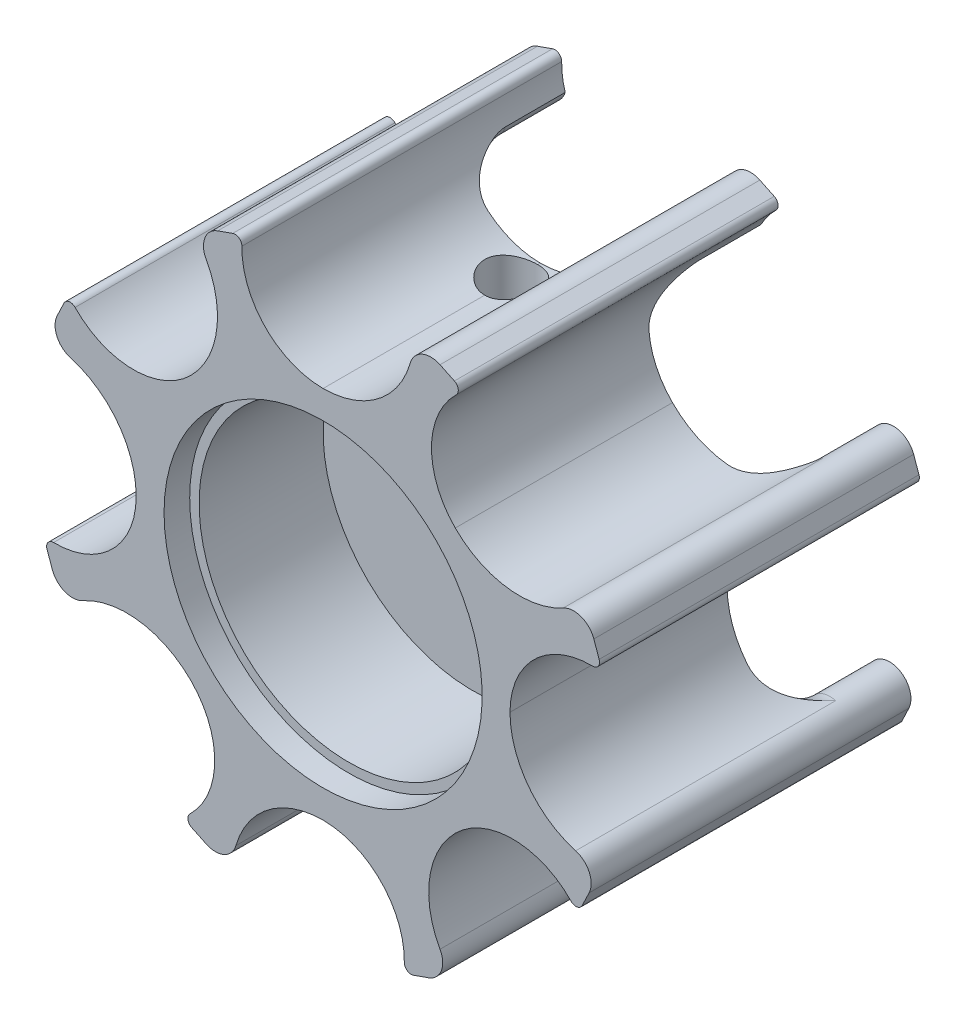
SolidWorks part; units mm, degrees
material "ABS"
ref_plane "前视基准面" through (0, 0, 0) normal (0, 0, 1) x (1, 0, 0)
ref_plane "上视基准面" through (0, 0, 0) normal (0, 1, 0) x (1, 0, 0)
ref_plane "右视基准面" through (0, 0, 0) normal (1, 0, 0) x (0, 0, -1)
sketch "草图1" plane through (0, 0, 0) normal (0, 0, 1) x (1, 0, 0)
  line L0 (0, 31.3575) -> (0, 0) construction
  line L1 (0, 0) -> (22.1731, 22.1731) construction
  line L4 (0, 31.3575) -> (22.1731, 22.1731) construction
  line L6 (11.6409, 26.5357) -> (12.5976, 28.8454) construction
  line L7 (21.7656, 23.184) -> (15.5687, 29.0018) construction
  line L8 (21.7656, 23.184) -> (27.9942, 29.8184) construction
  line L9 (15.357, 30.2989) -> (13.674, 31.1018)
  line L10 (32.2836, 10.5656) -> (31.6613, 12.3233)
  line L11 (30.2989, -15.357) -> (31.1018, -13.674)
  line L12 (10.5656, -32.2836) -> (12.3233, -31.6613)
  line L13 (-15.357, -30.2989) -> (-13.674, -31.1018)
  line L14 (-32.2836, -10.5656) -> (-31.6613, -12.3233)
  line L15 (-30.2989, 15.357) -> (-31.1018, 13.674)
  line L16 (-10.5656, 32.2836) -> (-12.3233, 31.6613)
  circle A0 centre (0, 0) radius 31.3575 construction
  arc A9 (15.5687, 29.0018) -> (15.4556, 15.4556) centre (22.1731, 22.1731) ccw
  circle A13 centre (0, 0) radius 40.9 construction
  arc A16 (15.5687, 29.0018) -> (15.357, 30.2989) centre (15.0125, 29.5769) ccw
  arc A17 (13.674, 31.1018) -> (10.1948, 29.5357) centre (12.5976, 28.8454) ccw
  arc A18 (0, 21.8575) -> (10.1948, 29.5357) centre (0, 32.4647) ccw
  arc A19 (31.5161, 9.4987) -> (21.8575, 0) centre (31.3575, 0) ccw
  arc A20 (31.5161, 9.4987) -> (32.2836, 10.5656) centre (31.5295, 10.2986) ccw
  arc A21 (31.6613, 12.3233) -> (28.0937, 13.6761) centre (29.3046, 11.4889) ccw
  arc A22 (15.4556, 15.4556) -> (28.0937, 13.6761) centre (22.956, 22.956) ccw
  arc A24 (29.0018, -15.5687) -> (15.4556, -15.4556) centre (22.1731, -22.1731) ccw
  arc A25 (29.0018, -15.5687) -> (30.2989, -15.357) centre (29.5769, -15.0125) ccw
  arc A26 (31.1018, -13.674) -> (29.5357, -10.1948) centre (28.8454, -12.5976) ccw
  arc A27 (21.8575, 0) -> (29.5357, -10.1948) centre (32.4647, 0) ccw
  arc A29 (9.4987, -31.5161) -> (0, -21.8575) centre (0, -31.3575) ccw
  arc A30 (9.4987, -31.5161) -> (10.5656, -32.2836) centre (10.2986, -31.5295) ccw
  arc A31 (12.3233, -31.6613) -> (13.6761, -28.0937) centre (11.4889, -29.3046) ccw
  arc A32 (15.4556, -15.4556) -> (13.6761, -28.0937) centre (22.956, -22.956) ccw
  arc A34 (-15.5687, -29.0018) -> (-15.4556, -15.4556) centre (-22.1731, -22.1731) ccw
  arc A35 (-15.5687, -29.0018) -> (-15.357, -30.2989) centre (-15.0125, -29.5769) ccw
  arc A36 (-13.674, -31.1018) -> (-10.1948, -29.5357) centre (-12.5976, -28.8454) ccw
  arc A37 (0, -21.8575) -> (-10.1948, -29.5357) centre (0, -32.4647) ccw
  arc A39 (-31.5161, -9.4987) -> (-21.8575, 0) centre (-31.3575, 0) ccw
  arc A40 (-31.5161, -9.4987) -> (-32.2836, -10.5656) centre (-31.5295, -10.2986) ccw
  arc A41 (-31.6613, -12.3233) -> (-28.0937, -13.6761) centre (-29.3046, -11.4889) ccw
  arc A42 (-15.4556, -15.4556) -> (-28.0937, -13.6761) centre (-22.956, -22.956) ccw
  arc A44 (-29.0018, 15.5687) -> (-15.4556, 15.4556) centre (-22.1731, 22.1731) ccw
  arc A45 (-29.0018, 15.5687) -> (-30.2989, 15.357) centre (-29.5769, 15.0125) ccw
  arc A46 (-31.1018, 13.674) -> (-29.5357, 10.1948) centre (-28.8454, 12.5976) ccw
  arc A47 (-21.8575, 0) -> (-29.5357, 10.1948) centre (-32.4647, 0) ccw
  arc A49 (-9.4987, 31.5161) -> (0, 21.8575) centre (0, 31.3575) ccw
  arc A50 (-9.4987, 31.5161) -> (-10.5656, 32.2836) centre (-10.2986, 31.5295) ccw
  arc A51 (-12.3233, 31.6613) -> (-13.6761, 28.0937) centre (-11.4889, 29.3046) ccw
  arc A52 (-15.4556, 15.4556) -> (-13.6761, 28.0937) centre (-22.956, 22.956) ccw
  point P98 (0, 0)
  dimension "D1" = 9.5
  dimension "D3" = 45
  dimension "D5" = 9.1
  dimension "D8" = 81.8
  dimension "D9" = 9.5
  dimension "D10" = 2.5
  dimension "D11" = 0.8
  dimension "D2" = 24
  dimension "D6" = 11.4
  dimension "D7" = 2.5
  dimension "D13" = 8.5
  dimension "D12" = 8
extrude "凸台-拉伸1" add sketch "草图1" along normal blind 27.5
sketch "草图2" plane through (0, 0, 0) normal (0, 0, -1) x (-1, 0, 0)
  line L0 (0, 0) -> (21.8575, 0) construction
  line L1 (0, 0) -> (15.4556, -15.4556) construction
  arc A0 (20.6575, 0) -> (24.8509, -8.4944) centre (31.3575, 0) ccw construction
  arc A1 (23.828, -11.1811) -> (14.6071, -14.6071) centre (22.956, -22.956) ccw construction
  arc A2 (23.828, -11.1811) -> (24.8509, -8.4944) centre (23.9388, -9.6852) ccw construction
  circle A3 centre (0, 0) radius 18.6
  arc A4 (28.0937, -13.6761) -> (15.4556, -15.4556) centre (22.956, -22.956) ccw construction
  arc A5 (21.8575, 0) -> (31.5161, -9.4987) centre (31.3575, 0) ccw construction
  arc A6 (14.6071, -14.6071) -> (11.5658, -23.5787) centre (22.1731, -22.1731) ccw construction
  arc A7 (8.9427, -24.7551) -> (0, -20.6575) centre (0, -32.4647) ccw construction
  arc A8 (8.9427, -24.7551) -> (11.5658, -23.5787) centre (10.0788, -23.7757) ccw construction
  arc A9 (0, -20.6575) -> (-8.4944, -24.8509) centre (0, -31.3575) ccw construction
  arc A10 (-11.1811, -23.828) -> (-14.6071, -14.6071) centre (-22.956, -22.956) ccw construction
  arc A11 (-11.1811, -23.828) -> (-8.4944, -24.8509) centre (-9.6852, -23.9388) ccw construction
  arc A12 (-14.6071, -14.6071) -> (-23.5787, -11.5658) centre (-22.1731, -22.1731) ccw construction
  arc A13 (-24.7551, -8.9427) -> (-20.6575, 0) centre (-32.4647, 0) ccw construction
  arc A14 (-24.7551, -8.9427) -> (-23.5787, -11.5658) centre (-23.7757, -10.0788) ccw construction
  arc A15 (-20.6575, 0) -> (-24.8509, 8.4944) centre (-31.3575, 0) ccw construction
  arc A16 (-23.828, 11.1811) -> (-14.6071, 14.6071) centre (-22.956, 22.956) ccw construction
  arc A17 (-23.828, 11.1811) -> (-24.8509, 8.4944) centre (-23.9388, 9.6852) ccw construction
  arc A18 (-14.6071, 14.6071) -> (-11.5658, 23.5787) centre (-22.1731, 22.1731) ccw construction
  arc A19 (-8.9427, 24.7551) -> (0, 20.6575) centre (0, 32.4647) ccw construction
  arc A20 (-8.9427, 24.7551) -> (-11.5658, 23.5787) centre (-10.0788, 23.7757) ccw construction
  arc A21 (0, 20.6575) -> (8.4944, 24.8509) centre (0, 31.3575) ccw construction
  arc A22 (11.1811, 23.828) -> (14.6071, 14.6071) centre (22.956, 22.956) ccw construction
  arc A23 (11.1811, 23.828) -> (8.4944, 24.8509) centre (9.6852, 23.9388) ccw construction
  arc A24 (14.6071, 14.6071) -> (23.5787, 11.5658) centre (22.1731, 22.1731) ccw construction
  arc A25 (24.7551, 8.9427) -> (20.6575, 0) centre (32.4647, 0) ccw construction
  arc A26 (24.7551, 8.9427) -> (23.5787, 11.5658) centre (23.7757, 10.0788) ccw construction
  point P72 (0, 0)
  dimension "D1" = 1.2
  dimension "D2" = 1.2
  dimension "D3" = 1.5
  dimension "D5" = 37.2
  dimension "D4" = 8
extrude "切除-拉伸1" cut sketch "草图2" against normal through all
sketch "草图3" plane through (0, 0, 0) normal (0, 0, -1) x (-1, 0, 0)
  line L8 (-31.6613, 12.3233) -> (-32.2836, 10.5656)
  line L9 (-31.1018, -13.674) -> (-30.2989, -15.357)
  line L10 (-12.3233, -31.6613) -> (-10.5656, -32.2836)
  line L11 (13.674, -31.1018) -> (15.357, -30.2989)
  line L12 (31.6613, -12.3233) -> (32.2836, -10.5656)
  line L13 (31.1018, 13.674) -> (30.2989, 15.357)
  line L14 (12.3233, 31.6613) -> (10.5656, 32.2836)
  line L15 (-13.674, 31.1018) -> (-15.357, 30.2989)
  line L16 (-31.6613, 12.3233) -> (-32.2836, 10.5656)
  line L17 (-31.1018, -13.674) -> (-30.2989, -15.357)
  line L18 (-12.3233, -31.6613) -> (-10.5656, -32.2836)
  line L19 (13.674, -31.1018) -> (15.357, -30.2989)
  line L20 (31.6613, -12.3233) -> (32.2836, -10.5656)
  line L21 (31.1018, 13.674) -> (30.2989, 15.357)
  line L22 (12.3233, 31.6613) -> (10.5656, 32.2836)
  line L23 (-13.674, 31.1018) -> (-15.357, 30.2989)
  circle A1 centre (0, 0) radius 3.2
  spline S32 degree 3 poles (-15.4556, 15.4556) (-18.9298, 11.9813) (-23.7952, 11.2963) (-28.0937, 13.6761) knots 0 0 0 0 1 1 1 1 weights 1 0.86586 0.86586 1
  spline S33 degree 3 poles (-15.4556, 15.4556) (-18.9298, 11.9813) (-23.7952, 11.2963) (-28.0937, 13.6761) knots 0 0 0 0 1 1 1 1 weights 1 0.86586 0.86586 1
  spline S34 degree 3 poles (-28.0937, 13.6761) (-29.5497, 14.4822) (-31.1058, 13.8921) (-31.6613, 12.3233) knots 0 0 0 0 1 1 1 1 weights 1 0.764197 0.764197 1
  spline S35 degree 3 poles (-28.0937, 13.6761) (-29.5497, 14.4822) (-31.1058, 13.8921) (-31.6613, 12.3233) knots 0 0 0 0 1 1 1 1 weights 1 0.764197 0.764197 1
  spline S36 degree 3 poles (-32.2836, 10.5656) (-32.4885, 9.9868) (-32.13, 9.4884) (-31.5161, 9.4987) knots 0 0 0 0 1 1 1 1 weights 1 0.713557 0.713557 1
  spline S37 degree 3 poles (-32.2836, 10.5656) (-32.4885, 9.9868) (-32.13, 9.4884) (-31.5161, 9.4987) knots 0 0 0 0 1 1 1 1 weights 1 0.713557 0.713557 1
  spline S38 degree 3 poles (-31.5161, 9.4987) (-25.878, 9.5928) (-21.8575, 5.6389) (-21.8575, 0) knots 0 0 0 0 1 1 1 1 weights 1 0.800786 0.800786 1
  spline S39 degree 3 poles (-31.5161, 9.4987) (-25.878, 9.5928) (-21.8575, 5.6389) (-21.8575, 0) knots 0 0 0 0 1 1 1 1 weights 1 0.800786 0.800786 1
  spline S40 degree 3 poles (-21.8575, 0) (-21.8575, -4.9133) (-24.8134, -8.8381) (-29.5357, -10.1948) knots 0 0 0 0 1 1 1 1 weights 1 0.86586 0.86586 1
  spline S41 degree 3 poles (-21.8575, 0) (-21.8575, -4.9133) (-24.8134, -8.8381) (-29.5357, -10.1948) knots 0 0 0 0 1 1 1 1 weights 1 0.86586 0.86586 1
  spline S42 degree 3 poles (-29.5357, -10.1948) (-31.1353, -10.6543) (-31.8184, -12.1719) (-31.1018, -13.674) knots 0 0 0 0 1 1 1 1 weights 1 0.764197 0.764197 1
  spline S43 degree 3 poles (-29.5357, -10.1948) (-31.1353, -10.6543) (-31.8184, -12.1719) (-31.1018, -13.674) knots 0 0 0 0 1 1 1 1 weights 1 0.764197 0.764197 1
  spline S44 degree 3 poles (-30.2989, -15.357) (-30.0346, -15.9111) (-29.4287, -16.01) (-29.0018, -15.5687) knots 0 0 0 0 1 1 1 1 weights 1 0.713557 0.713557 1
  spline S45 degree 3 poles (-30.2989, -15.357) (-30.0346, -15.9111) (-29.4287, -16.01) (-29.0018, -15.5687) knots 0 0 0 0 1 1 1 1 weights 1 0.713557 0.713557 1
  spline S46 degree 3 poles (-29.0018, -15.5687) (-25.0816, -11.5153) (-19.4429, -11.4683) (-15.4556, -15.4556) knots 0 0 0 0 1 1 1 1 weights 1 0.800786 0.800786 1
  spline S47 degree 3 poles (-29.0018, -15.5687) (-25.0816, -11.5153) (-19.4429, -11.4683) (-15.4556, -15.4556) knots 0 0 0 0 1 1 1 1 weights 1 0.800786 0.800786 1
  spline S48 degree 3 poles (-15.4556, -15.4556) (-11.9813, -18.9298) (-11.2963, -23.7952) (-13.6761, -28.0937) knots 0 0 0 0 1 1 1 1 weights 1 0.86586 0.86586 1
  spline S49 degree 3 poles (-15.4556, -15.4556) (-11.9813, -18.9298) (-11.2963, -23.7952) (-13.6761, -28.0937) knots 0 0 0 0 1 1 1 1 weights 1 0.86586 0.86586 1
  spline S50 degree 3 poles (-13.6761, -28.0937) (-14.4822, -29.5497) (-13.8921, -31.1058) (-12.3233, -31.6613) knots 0 0 0 0 1 1 1 1 weights 1 0.764197 0.764197 1
  spline S51 degree 3 poles (-13.6761, -28.0937) (-14.4822, -29.5497) (-13.8921, -31.1058) (-12.3233, -31.6613) knots 0 0 0 0 1 1 1 1 weights 1 0.764197 0.764197 1
  spline S52 degree 3 poles (-10.5656, -32.2836) (-9.9868, -32.4885) (-9.4884, -32.13) (-9.4987, -31.5161) knots 0 0 0 0 1 1 1 1 weights 1 0.713557 0.713557 1
  spline S53 degree 3 poles (-10.5656, -32.2836) (-9.9868, -32.4885) (-9.4884, -32.13) (-9.4987, -31.5161) knots 0 0 0 0 1 1 1 1 weights 1 0.713557 0.713557 1
  spline S54 degree 3 poles (-9.4987, -31.5161) (-9.5928, -25.878) (-5.6389, -21.8575) (0, -21.8575) knots 0 0 0 0 1 1 1 1 weights 1 0.800786 0.800786 1
  spline S55 degree 3 poles (-9.4987, -31.5161) (-9.5928, -25.878) (-5.6389, -21.8575) (0, -21.8575) knots 0 0 0 0 1 1 1 1 weights 1 0.800786 0.800786 1
  spline S56 degree 3 poles (0, -21.8575) (4.9133, -21.8575) (8.8381, -24.8134) (10.1948, -29.5357) knots 0 0 0 0 1 1 1 1 weights 1 0.86586 0.86586 1
  spline S57 degree 3 poles (0, -21.8575) (4.9133, -21.8575) (8.8381, -24.8134) (10.1948, -29.5357) knots 0 0 0 0 1 1 1 1 weights 1 0.86586 0.86586 1
  spline S58 degree 3 poles (10.1948, -29.5357) (10.6543, -31.1353) (12.1719, -31.8184) (13.674, -31.1018) knots 0 0 0 0 1 1 1 1 weights 1 0.764197 0.764197 1
  spline S59 degree 3 poles (10.1948, -29.5357) (10.6543, -31.1353) (12.1719, -31.8184) (13.674, -31.1018) knots 0 0 0 0 1 1 1 1 weights 1 0.764197 0.764197 1
  spline S60 degree 3 poles (15.357, -30.2989) (15.9111, -30.0346) (16.01, -29.4287) (15.5687, -29.0018) knots 0 0 0 0 1 1 1 1 weights 1 0.713557 0.713557 1
  spline S61 degree 3 poles (15.357, -30.2989) (15.9111, -30.0346) (16.01, -29.4287) (15.5687, -29.0018) knots 0 0 0 0 1 1 1 1 weights 1 0.713557 0.713557 1
  spline S62 degree 3 poles (15.5687, -29.0018) (11.5153, -25.0816) (11.4683, -19.4429) (15.4556, -15.4556) knots 0 0 0 0 1 1 1 1 weights 1 0.800786 0.800786 1
  spline S63 degree 3 poles (15.5687, -29.0018) (11.5153, -25.0816) (11.4683, -19.4429) (15.4556, -15.4556) knots 0 0 0 0 1 1 1 1 weights 1 0.800786 0.800786 1
  spline S64 degree 3 poles (15.4556, -15.4556) (18.9298, -11.9813) (23.7952, -11.2963) (28.0937, -13.6761) knots 0 0 0 0 1 1 1 1 weights 1 0.86586 0.86586 1
  spline S65 degree 3 poles (15.4556, -15.4556) (18.9298, -11.9813) (23.7952, -11.2963) (28.0937, -13.6761) knots 0 0 0 0 1 1 1 1 weights 1 0.86586 0.86586 1
  spline S66 degree 3 poles (28.0937, -13.6761) (29.5497, -14.4822) (31.1058, -13.8921) (31.6613, -12.3233) knots 0 0 0 0 1 1 1 1 weights 1 0.764197 0.764197 1
  spline S67 degree 3 poles (28.0937, -13.6761) (29.5497, -14.4822) (31.1058, -13.8921) (31.6613, -12.3233) knots 0 0 0 0 1 1 1 1 weights 1 0.764197 0.764197 1
  spline S68 degree 3 poles (32.2836, -10.5656) (32.4885, -9.9868) (32.13, -9.4884) (31.5161, -9.4987) knots 0 0 0 0 1 1 1 1 weights 1 0.713557 0.713557 1
  spline S69 degree 3 poles (32.2836, -10.5656) (32.4885, -9.9868) (32.13, -9.4884) (31.5161, -9.4987) knots 0 0 0 0 1 1 1 1 weights 1 0.713557 0.713557 1
  spline S70 degree 3 poles (31.5161, -9.4987) (25.878, -9.5928) (21.8575, -5.6389) (21.8575, 0) knots 0 0 0 0 1 1 1 1 weights 1 0.800786 0.800786 1
  spline S71 degree 3 poles (31.5161, -9.4987) (25.878, -9.5928) (21.8575, -5.6389) (21.8575, 0) knots 0 0 0 0 1 1 1 1 weights 1 0.800786 0.800786 1
  spline S72 degree 3 poles (21.8575, 0) (21.8575, 4.9133) (24.8134, 8.8381) (29.5357, 10.1948) knots 0 0 0 0 1 1 1 1 weights 1 0.86586 0.86586 1
  spline S73 degree 3 poles (21.8575, 0) (21.8575, 4.9133) (24.8134, 8.8381) (29.5357, 10.1948) knots 0 0 0 0 1 1 1 1 weights 1 0.86586 0.86586 1
  spline S74 degree 3 poles (29.5357, 10.1948) (31.1353, 10.6543) (31.8184, 12.1719) (31.1018, 13.674) knots 0 0 0 0 1 1 1 1 weights 1 0.764197 0.764197 1
  spline S75 degree 3 poles (29.5357, 10.1948) (31.1353, 10.6543) (31.8184, 12.1719) (31.1018, 13.674) knots 0 0 0 0 1 1 1 1 weights 1 0.764197 0.764197 1
  spline S76 degree 3 poles (30.2989, 15.357) (30.0346, 15.9111) (29.4287, 16.01) (29.0018, 15.5687) knots 0 0 0 0 1 1 1 1 weights 1 0.713557 0.713557 1
  spline S77 degree 3 poles (30.2989, 15.357) (30.0346, 15.9111) (29.4287, 16.01) (29.0018, 15.5687) knots 0 0 0 0 1 1 1 1 weights 1 0.713557 0.713557 1
  spline S78 degree 3 poles (29.0018, 15.5687) (25.0816, 11.5153) (19.4429, 11.4683) (15.4556, 15.4556) knots 0 0 0 0 1 1 1 1 weights 1 0.800786 0.800786 1
  spline S79 degree 3 poles (29.0018, 15.5687) (25.0816, 11.5153) (19.4429, 11.4683) (15.4556, 15.4556) knots 0 0 0 0 1 1 1 1 weights 1 0.800786 0.800786 1
  spline S80 degree 3 poles (15.4556, 15.4556) (11.9813, 18.9298) (11.2963, 23.7952) (13.6761, 28.0937) knots 0 0 0 0 1 1 1 1 weights 1 0.86586 0.86586 1
  spline S81 degree 3 poles (15.4556, 15.4556) (11.9813, 18.9298) (11.2963, 23.7952) (13.6761, 28.0937) knots 0 0 0 0 1 1 1 1 weights 1 0.86586 0.86586 1
  spline S82 degree 3 poles (13.6761, 28.0937) (14.4822, 29.5497) (13.8921, 31.1058) (12.3233, 31.6613) knots 0 0 0 0 1 1 1 1 weights 1 0.764197 0.764197 1
  spline S83 degree 3 poles (13.6761, 28.0937) (14.4822, 29.5497) (13.8921, 31.1058) (12.3233, 31.6613) knots 0 0 0 0 1 1 1 1 weights 1 0.764197 0.764197 1
  spline S84 degree 3 poles (10.5656, 32.2836) (9.9868, 32.4885) (9.4884, 32.13) (9.4987, 31.5161) knots 0 0 0 0 1 1 1 1 weights 1 0.713557 0.713557 1
  spline S85 degree 3 poles (10.5656, 32.2836) (9.9868, 32.4885) (9.4884, 32.13) (9.4987, 31.5161) knots 0 0 0 0 1 1 1 1 weights 1 0.713557 0.713557 1
  spline S86 degree 3 poles (9.4987, 31.5161) (9.5928, 25.878) (5.6389, 21.8575) (0, 21.8575) knots 0 0 0 0 1 1 1 1 weights 1 0.800786 0.800786 1
  spline S87 degree 3 poles (9.4987, 31.5161) (9.5928, 25.878) (5.6389, 21.8575) (0, 21.8575) knots 0 0 0 0 1 1 1 1 weights 1 0.800786 0.800786 1
  spline S88 degree 3 poles (0, 21.8575) (-4.9133, 21.8575) (-8.8381, 24.8134) (-10.1948, 29.5357) knots 0 0 0 0 1 1 1 1 weights 1 0.86586 0.86586 1
  spline S89 degree 3 poles (0, 21.8575) (-4.9133, 21.8575) (-8.8381, 24.8134) (-10.1948, 29.5357) knots 0 0 0 0 1 1 1 1 weights 1 0.86586 0.86586 1
  spline S90 degree 3 poles (-10.1948, 29.5357) (-10.6543, 31.1353) (-12.1719, 31.8184) (-13.674, 31.1018) knots 0 0 0 0 1 1 1 1 weights 1 0.764197 0.764197 1
  spline S91 degree 3 poles (-10.1948, 29.5357) (-10.6543, 31.1353) (-12.1719, 31.8184) (-13.674, 31.1018) knots 0 0 0 0 1 1 1 1 weights 1 0.764197 0.764197 1
  spline S92 degree 3 poles (-15.357, 30.2989) (-15.9111, 30.0346) (-16.01, 29.4287) (-15.5687, 29.0018) knots 0 0 0 0 1 1 1 1 weights 1 0.713557 0.713557 1
  spline S93 degree 3 poles (-15.357, 30.2989) (-15.9111, 30.0346) (-16.01, 29.4287) (-15.5687, 29.0018) knots 0 0 0 0 1 1 1 1 weights 1 0.713557 0.713557 1
  spline S94 degree 3 poles (-15.5687, 29.0018) (-11.5153, 25.0816) (-11.4683, 19.4429) (-15.4556, 15.4556) knots 0 0 0 0 1 1 1 1 weights 1 0.800786 0.800786 1
  spline S95 degree 3 poles (-15.5687, 29.0018) (-11.5153, 25.0816) (-11.4683, 19.4429) (-15.4556, 15.4556) knots 0 0 0 0 1 1 1 1 weights 1 0.800786 0.800786 1
  dimension "D2" = 6.4
  dimension "D1" = 0
extrude "凸台-拉伸2" add sketch "草图3" along normal blind 4 and the other way blind 10
sketch "草图6" plane through (0, 0, 10) normal (0, 0, 1) x (1, 0, 0)
  circle A0 centre (0, 0) radius 17.5
  circle A1 centre (0, 0) radius 18.6
  circle A2 centre (0, 0) radius 18.6 construction
  dimension "D1" = 35
extrude "凸台-拉伸3" add sketch "草图6" along normal offset from surface (14.5 mm away) 28.5 up to face at (0, 0, -4)
sketch "草图8" plane through (0, 0, -4) normal (0, 0, -1) x (-1, 0, 0)
  line L0 (-1.9975, 2.5) -> (1.9975, 2.5)
  line L1 (-1.9975, 2.5) -> (-1.9975, 3.2)
  line L2 (-1.9975, 3.2) -> (1.9975, 3.2)
  line L3 (1.9975, 3.2) -> (1.9975, 2.5)
  circle A5 centre (0, 0) radius 3.2 construction
  spline S2 degree 3 poles (-3.1998, -0.0461) (-3.1941, -0.4188) (-3.0765, -1.0381) (-2.6711, -1.8139) (-2.0182, -2.5712) (-1.1275, -3.0679) (-0.1399, -3.226) (0.6074, -3.1714) (1.5616, -2.8713) (2.3704, -2.2505) (2.9067, -1.4063) (3.1529, -0.6983) (3.2288, 0.0477) (3.1309, 0.7911) (2.8639, 1.4915) (2.3029, 2.3195) (1.4761, 2.9162) (0.5135, 3.188) (-0.2351, 3.2205) (-1.2177, 3.0332) (-2.093, 2.5105) (-2.7239, 1.7342) (-3.0502, 1.0596) (-3.1859, 0.4499) (-3.2017, 0.0776) (-3.1998, -0.0461) (-3.1941, -0.4188) (-3.0765, -1.0381) knots 3.025237 3.141215 3.141215 3.141215 3.490659 3.723369 3.95608 4.421501 4.654211 4.886922 5.119632 5.585054 5.817764 6.050475 6.283185 6.515896 6.748606 6.981317 7.446738 7.679449 7.912159 8.14487 8.610291 8.843002 9.075712 9.308423 9.4244 9.4244 9.4244 9.773844 10.006554 10.239265 only from (-3.1998, -0.0461) to (-3.1998, -0.0461) construction
  dimension "D1" = 2.5
extrude "凸台-拉伸5" add sketch "草图8" against normal up to surface (14 mm away) up to face at (-3.2, 0, 10)
sketch "草图4" plane through (0, 2.5, 0) normal (0, -1, 0) x (1, 0, 0)
  line L1 (-10.1948, -4) -> (0, -4) construction
  circle A0 centre (0, 5.5) radius 1.5
  dimension "D1" = 3
  dimension "D2" = 9.5
extrude "切除-拉伸2" cut sketch "草图4" against normal through all and the other way through all
sketch "草图5" plane through (0, 2.5, 0) normal (0, -1, 0) x (1, 0, 0)
  circle A0 centre (0, 5.5) radius 3.1
  dimension "D1" = 6.2
extrude "切除-拉伸6" cut sketch "草图5" against normal through all from offset 10 offset against normal yes
sketch "草图10" plane through (0, 0, 10) normal (0, 0, 1) x (1, 0, 0)
  circle A0 centre (0, 0) radius 3.2
  arc A1 (-1.9975, 2.5) -> (1.9975, 2.5) centre (0, 0) ccw construction
extrude "切除-拉伸7" cut sketch "草图10" against normal blind 2
sketch "草图11" plane through (0, 0, -4) normal (0, 0, -1) x (-1, 0, 0)
  line L8 (-31.6613, 12.3233) -> (-32.2836, 10.5656)
  line L9 (-31.1018, -13.674) -> (-30.2989, -15.357)
  line L10 (-12.3233, -31.6613) -> (-10.5656, -32.2836)
  line L11 (13.674, -31.1018) -> (15.357, -30.2989)
  line L12 (31.6613, -12.3233) -> (32.2836, -10.5656)
  line L13 (31.1018, 13.674) -> (30.2989, 15.357)
  line L14 (12.3233, 31.6613) -> (10.5656, 32.2836)
  line L15 (-13.674, 31.1018) -> (-15.357, 30.2989)
  arc A0 (-10.1948, 29.5357) -> (-13.7944, 26.6505) centre (-12.5976, 28.8454) cw
  arc A1 (13.6761, 28.0937) -> (9.0906, 28.5988) centre (11.4889, 29.3046) cw
  arc A2 (-15.4556, 15.4556) -> (-15.5687, 29.0018) centre (-22.1731, 22.1731) ccw construction
  arc A3 (29.5357, 10.1948) -> (26.6505, 13.7944) centre (28.8454, 12.5976) cw
  arc A4 (28.0937, -13.6761) -> (28.5988, -9.0906) centre (29.3046, -11.4889) cw
  arc A5 (10.1948, -29.5357) -> (13.7944, -26.6505) centre (12.5976, -28.8454) cw
  arc A6 (-13.6761, -28.0937) -> (-9.0906, -28.5988) centre (-11.4889, -29.3046) cw
  arc A7 (-29.5357, -10.1948) -> (-26.6505, -13.7944) centre (-28.8454, -12.5976) cw
  arc A8 (-28.0937, 13.6761) -> (-28.5988, 9.0906) centre (-29.3046, 11.4889) cw
  arc A32 (-28.0937, 13.6761) -> (-31.6613, 12.3233) centre (-29.3046, 11.4889) ccw
  arc A33 (-32.2836, 10.5656) -> (-31.5161, 9.4987) centre (-31.5295, 10.2986) ccw
  arc A34 (-21.8575, 0) -> (-31.5161, 9.4987) centre (-31.3575, 0) ccw
  arc A35 (-29.5357, -10.1948) -> (-21.8575, 0) centre (-32.4647, 0) ccw
  arc A36 (-29.5357, -10.1948) -> (-31.1018, -13.674) centre (-28.8454, -12.5976) ccw
  arc A37 (-30.2989, -15.357) -> (-29.0018, -15.5687) centre (-29.5769, -15.0125) ccw
  arc A38 (-15.4556, -15.4556) -> (-29.0018, -15.5687) centre (-22.1731, -22.1731) ccw
  arc A39 (-13.6761, -28.0937) -> (-15.4556, -15.4556) centre (-22.956, -22.956) ccw
  arc A40 (-13.6761, -28.0937) -> (-12.3233, -31.6613) centre (-11.4889, -29.3046) ccw
  arc A41 (-10.5656, -32.2836) -> (-9.4987, -31.5161) centre (-10.2986, -31.5295) ccw
  arc A42 (0, -21.8575) -> (-9.4987, -31.5161) centre (0, -31.3575) ccw
  arc A43 (10.1948, -29.5357) -> (0, -21.8575) centre (0, -32.4647) ccw
  arc A44 (10.1948, -29.5357) -> (13.674, -31.1018) centre (12.5976, -28.8454) ccw
  arc A45 (15.357, -30.2989) -> (15.5687, -29.0018) centre (15.0125, -29.5769) ccw
  arc A46 (15.4556, -15.4556) -> (15.5687, -29.0018) centre (22.1731, -22.1731) ccw
  arc A47 (28.0937, -13.6761) -> (15.4556, -15.4556) centre (22.956, -22.956) ccw
  arc A48 (28.0937, -13.6761) -> (31.6613, -12.3233) centre (29.3046, -11.4889) ccw
  arc A49 (32.2836, -10.5656) -> (31.5161, -9.4987) centre (31.5295, -10.2986) ccw
  arc A50 (21.8575, 0) -> (31.5161, -9.4987) centre (31.3575, 0) ccw
  arc A51 (29.5357, 10.1948) -> (21.8575, 0) centre (32.4647, 0) ccw
  arc A52 (29.5357, 10.1948) -> (31.1018, 13.674) centre (28.8454, 12.5976) ccw
  arc A53 (30.2989, 15.357) -> (29.0018, 15.5687) centre (29.5769, 15.0125) ccw
  arc A54 (15.4556, 15.4556) -> (29.0018, 15.5687) centre (22.1731, 22.1731) ccw
  arc A55 (13.6761, 28.0937) -> (15.4556, 15.4556) centre (22.956, 22.956) ccw
  arc A56 (13.6761, 28.0937) -> (12.3233, 31.6613) centre (11.4889, 29.3046) ccw
  arc A57 (10.5656, 32.2836) -> (9.4987, 31.5161) centre (10.2986, 31.5295) ccw
  arc A58 (0, 21.8575) -> (9.4987, 31.5161) centre (0, 31.3575) ccw
  arc A59 (-10.1948, 29.5357) -> (0, 21.8575) centre (0, 32.4647) ccw
  arc A60 (-10.1948, 29.5357) -> (-13.674, 31.1018) centre (-12.5976, 28.8454) ccw
  arc A61 (-15.357, 30.2989) -> (-15.5687, 29.0018) centre (-15.0125, 29.5769) ccw
  arc A62 (-15.4556, 15.4556) -> (-15.5687, 29.0018) centre (-22.1731, 22.1731) ccw
  arc A63 (-28.0937, 13.6761) -> (-15.4556, 15.4556) centre (-22.956, 22.956) ccw
  arc A66 (-21.8575, 0) -> (-28.5988, 9.0906) centre (-31.3575, 0) ccw
  arc A67 (-29.5357, -10.1948) -> (-21.8575, 0) centre (-32.4647, 0) ccw
  arc A70 (-15.4556, -15.4556) -> (-26.6505, -13.7944) centre (-22.1731, -22.1731) ccw
  arc A71 (-13.6761, -28.0937) -> (-15.4556, -15.4556) centre (-22.956, -22.956) ccw
  arc A74 (0, -21.8575) -> (-9.0906, -28.5988) centre (0, -31.3575) ccw
  arc A75 (10.1948, -29.5357) -> (0, -21.8575) centre (0, -32.4647) ccw
  arc A78 (15.4556, -15.4556) -> (13.7944, -26.6505) centre (22.1731, -22.1731) ccw
  arc A79 (28.0937, -13.6761) -> (15.4556, -15.4556) centre (22.956, -22.956) ccw
  arc A82 (21.8575, 0) -> (28.5988, -9.0906) centre (31.3575, 0) ccw
  arc A83 (29.5357, 10.1948) -> (21.8575, 0) centre (32.4647, 0) ccw
  arc A86 (15.4556, 15.4556) -> (26.6505, 13.7944) centre (22.1731, 22.1731) ccw
  arc A87 (13.6761, 28.0937) -> (15.4556, 15.4556) centre (22.956, 22.956) ccw
  arc A90 (0, 21.8575) -> (9.0906, 28.5988) centre (0, 31.3575) ccw
  arc A91 (-10.1948, 29.5357) -> (0, 21.8575) centre (0, 32.4647) ccw
  arc A94 (-15.4556, 15.4556) -> (-13.7944, 26.6505) centre (-22.1731, 22.1731) ccw
  arc A95 (-28.0937, 13.6761) -> (-15.4556, 15.4556) centre (-22.956, 22.956) ccw
  dimension "D2" = 8
  dimension "D1" = 0
extrude "切除-拉伸8" cut sketch "草图11" against normal offset from surface (6.1 mm away) 25.4 up to face at (-18.6, 0, 27.5)
sketch "草图12" plane through (0, 0, -4) normal (0, 0, -1) x (-1, 0, 0)
  line L0 (-31.6613, 12.3233) -> (-32.2836, 10.5656) construction
  line L1 (-31.1018, -13.674) -> (-30.2989, -15.357) construction
  line L2 (-12.3233, -31.6613) -> (-10.5656, -32.2836) construction
  line L3 (13.674, -31.1018) -> (15.357, -30.2989) construction
  line L4 (31.6613, -12.3233) -> (32.2836, -10.5656) construction
  line L5 (31.1018, 13.674) -> (30.2989, 15.357) construction
  line L6 (12.3233, 31.6613) -> (10.5656, 32.2836) construction
  line L7 (-13.674, 31.1018) -> (-15.357, 30.2989) construction
  line L8 (-31.6613, 12.3233) -> (-32.2836, 10.5656)
  line L9 (-31.1018, -13.674) -> (-30.2989, -15.357)
  line L10 (-12.3233, -31.6613) -> (-10.5656, -32.2836)
  line L11 (13.674, -31.1018) -> (15.357, -30.2989)
  line L12 (31.6613, -12.3233) -> (32.2836, -10.5656)
  line L13 (31.1018, 13.674) -> (30.2989, 15.357)
  line L14 (12.3233, 31.6613) -> (10.5656, 32.2836)
  line L15 (-13.674, 31.1018) -> (-15.357, 30.2989)
  arc A0 (-28.5988, 9.0906) -> (-31.5161, 9.4987) centre (-31.3575, 0) ccw construction
  arc A1 (-28.5988, 9.0906) -> (-28.0937, 13.6761) centre (-29.3046, 11.4889) ccw construction
  arc A2 (-28.0937, 13.6761) -> (-31.6613, 12.3233) centre (-29.3046, 11.4889) ccw construction
  arc A3 (-32.2836, 10.5656) -> (-31.5161, 9.4987) centre (-31.5295, 10.2986) ccw construction
  arc A4 (-26.6505, -13.7944) -> (-29.0018, -15.5687) centre (-22.1731, -22.1731) ccw construction
  arc A5 (-26.6505, -13.7944) -> (-29.5357, -10.1948) centre (-28.8454, -12.5976) ccw construction
  arc A6 (-29.5357, -10.1948) -> (-31.1018, -13.674) centre (-28.8454, -12.5976) ccw construction
  arc A7 (-30.2989, -15.357) -> (-29.0018, -15.5687) centre (-29.5769, -15.0125) ccw construction
  arc A8 (-9.0906, -28.5988) -> (-9.4987, -31.5161) centre (0, -31.3575) ccw construction
  arc A9 (-9.0906, -28.5988) -> (-13.6761, -28.0937) centre (-11.4889, -29.3046) ccw construction
  arc A10 (-13.6761, -28.0937) -> (-12.3233, -31.6613) centre (-11.4889, -29.3046) ccw construction
  arc A11 (-10.5656, -32.2836) -> (-9.4987, -31.5161) centre (-10.2986, -31.5295) ccw construction
  arc A12 (13.7944, -26.6505) -> (15.5687, -29.0018) centre (22.1731, -22.1731) ccw construction
  arc A13 (13.7944, -26.6505) -> (10.1948, -29.5357) centre (12.5976, -28.8454) ccw construction
  arc A14 (10.1948, -29.5357) -> (13.674, -31.1018) centre (12.5976, -28.8454) ccw construction
  arc A15 (15.357, -30.2989) -> (15.5687, -29.0018) centre (15.0125, -29.5769) ccw construction
  arc A16 (28.5988, -9.0906) -> (31.5161, -9.4987) centre (31.3575, 0) ccw construction
  arc A17 (28.5988, -9.0906) -> (28.0937, -13.6761) centre (29.3046, -11.4889) ccw construction
  arc A18 (28.0937, -13.6761) -> (31.6613, -12.3233) centre (29.3046, -11.4889) ccw construction
  arc A19 (32.2836, -10.5656) -> (31.5161, -9.4987) centre (31.5295, -10.2986) ccw construction
  arc A20 (26.6505, 13.7944) -> (29.0018, 15.5687) centre (22.1731, 22.1731) ccw construction
  arc A21 (26.6505, 13.7944) -> (29.5357, 10.1948) centre (28.8454, 12.5976) ccw construction
  arc A22 (29.5357, 10.1948) -> (31.1018, 13.674) centre (28.8454, 12.5976) ccw construction
  arc A23 (30.2989, 15.357) -> (29.0018, 15.5687) centre (29.5769, 15.0125) ccw construction
  arc A24 (9.0906, 28.5988) -> (9.4987, 31.5161) centre (0, 31.3575) ccw construction
  arc A25 (9.0906, 28.5988) -> (13.6761, 28.0937) centre (11.4889, 29.3046) ccw construction
  arc A26 (13.6761, 28.0937) -> (12.3233, 31.6613) centre (11.4889, 29.3046) ccw construction
  arc A27 (10.5656, 32.2836) -> (9.4987, 31.5161) centre (10.2986, 31.5295) ccw construction
  arc A28 (-13.7944, 26.6505) -> (-15.5687, 29.0018) centre (-22.1731, 22.1731) ccw construction
  arc A29 (-13.7944, 26.6505) -> (-10.1948, 29.5357) centre (-12.5976, 28.8454) ccw construction
  arc A30 (-10.1948, 29.5357) -> (-13.674, 31.1018) centre (-12.5976, 28.8454) ccw construction
  arc A31 (-15.357, 30.2989) -> (-15.5687, 29.0018) centre (-15.0125, 29.5769) ccw construction
  arc A32 (-28.5988, 9.0906) -> (-31.5161, 9.4987) centre (-31.3575, 0) ccw
  arc A33 (-28.5988, 9.0906) -> (-28.0937, 13.6761) centre (-29.3046, 11.4889) ccw
  arc A34 (-28.0937, 13.6761) -> (-31.6613, 12.3233) centre (-29.3046, 11.4889) ccw
  arc A35 (-32.2836, 10.5656) -> (-31.5161, 9.4987) centre (-31.5295, 10.2986) ccw
  arc A36 (-26.6505, -13.7944) -> (-29.0018, -15.5687) centre (-22.1731, -22.1731) ccw
  arc A37 (-26.6505, -13.7944) -> (-29.5357, -10.1948) centre (-28.8454, -12.5976) ccw
  arc A38 (-29.5357, -10.1948) -> (-31.1018, -13.674) centre (-28.8454, -12.5976) ccw
  arc A39 (-30.2989, -15.357) -> (-29.0018, -15.5687) centre (-29.5769, -15.0125) ccw
  arc A40 (-9.0906, -28.5988) -> (-9.4987, -31.5161) centre (0, -31.3575) ccw
  arc A41 (-9.0906, -28.5988) -> (-13.6761, -28.0937) centre (-11.4889, -29.3046) ccw
  arc A42 (-13.6761, -28.0937) -> (-12.3233, -31.6613) centre (-11.4889, -29.3046) ccw
  arc A43 (-10.5656, -32.2836) -> (-9.4987, -31.5161) centre (-10.2986, -31.5295) ccw
  arc A44 (13.7944, -26.6505) -> (15.5687, -29.0018) centre (22.1731, -22.1731) ccw
  arc A45 (13.7944, -26.6505) -> (10.1948, -29.5357) centre (12.5976, -28.8454) ccw
  arc A46 (10.1948, -29.5357) -> (13.674, -31.1018) centre (12.5976, -28.8454) ccw
  arc A47 (15.357, -30.2989) -> (15.5687, -29.0018) centre (15.0125, -29.5769) ccw
  arc A48 (28.5988, -9.0906) -> (31.5161, -9.4987) centre (31.3575, 0) ccw
  arc A49 (28.5988, -9.0906) -> (28.0937, -13.6761) centre (29.3046, -11.4889) ccw
  arc A50 (28.0937, -13.6761) -> (31.6613, -12.3233) centre (29.3046, -11.4889) ccw
  arc A51 (32.2836, -10.5656) -> (31.5161, -9.4987) centre (31.5295, -10.2986) ccw
  arc A52 (26.6505, 13.7944) -> (29.0018, 15.5687) centre (22.1731, 22.1731) ccw
  arc A53 (26.6505, 13.7944) -> (29.5357, 10.1948) centre (28.8454, 12.5976) ccw
  arc A54 (29.5357, 10.1948) -> (31.1018, 13.674) centre (28.8454, 12.5976) ccw
  arc A55 (30.2989, 15.357) -> (29.0018, 15.5687) centre (29.5769, 15.0125) ccw
  arc A56 (9.0906, 28.5988) -> (9.4987, 31.5161) centre (0, 31.3575) ccw
  arc A57 (9.0906, 28.5988) -> (13.6761, 28.0937) centre (11.4889, 29.3046) ccw
  arc A58 (13.6761, 28.0937) -> (12.3233, 31.6613) centre (11.4889, 29.3046) ccw
  arc A59 (10.5656, 32.2836) -> (9.4987, 31.5161) centre (10.2986, 31.5295) ccw
  arc A60 (-13.7944, 26.6505) -> (-15.5687, 29.0018) centre (-22.1731, 22.1731) ccw
  arc A61 (-13.7944, 26.6505) -> (-10.1948, 29.5357) centre (-12.5976, 28.8454) ccw
  arc A62 (-10.1948, 29.5357) -> (-13.674, 31.1018) centre (-12.5976, 28.8454) ccw
  arc A63 (-15.357, 30.2989) -> (-15.5687, 29.0018) centre (-15.0125, 29.5769) ccw
extrude "凸台-拉伸7" add sketch "草图12" along normal blind 12 from surface starting at face at (1.9975, 2.5, 2.1)
fillet "圆角1" radius 5 8 edges at (26.8196, 11.2152, 2.1) (26.8947, -11.034, 2.1) (11.2152, -26.8196, 2.1) (-11.034, -26.8947, 2.1) (-26.8196, -11.2152, 2.1) (-26.8947, 11.034, 2.1) (11.034, 26.8947, 2.1) (-11.2152, 26.8196, 2.1)
